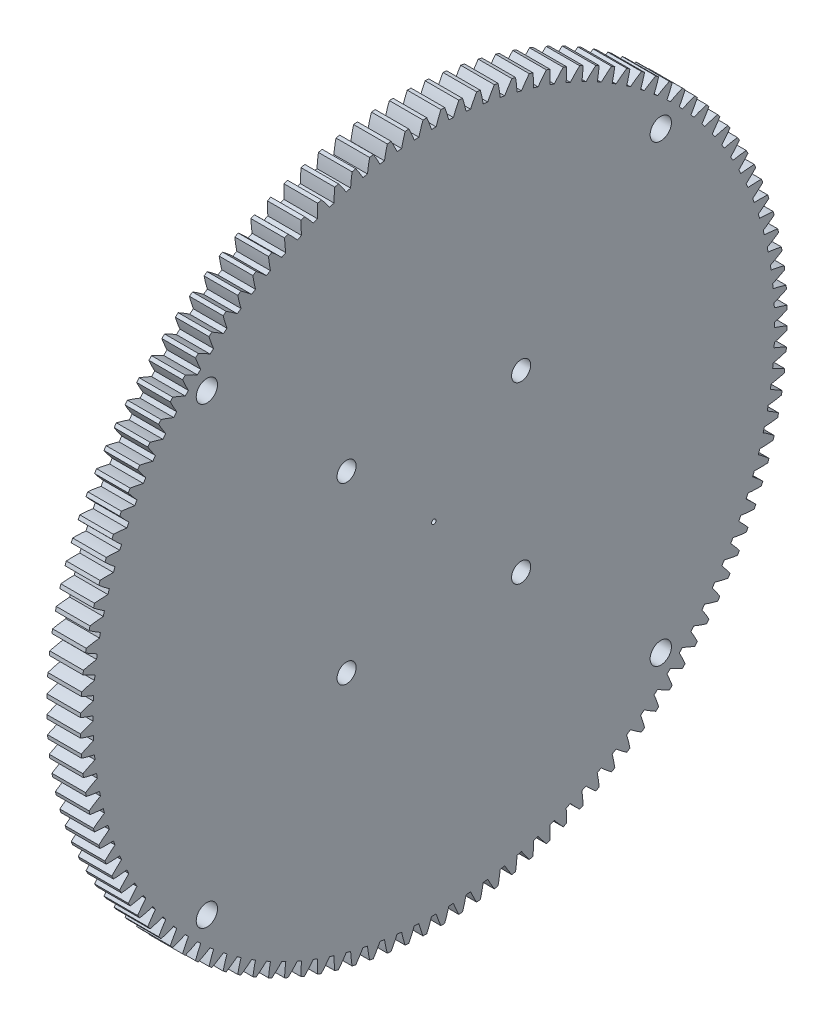
SolidWorks part; units mm, degrees
ref_plane "Plane1" through (0, 0, 0) normal (0, 0, 1) x (1, 0, 0)
ref_plane "Plane2" through (0, 0, 0) normal (0, 1, 0) x (1, 0, 0)
ref_plane "Plane3" through (0, 0, 0) normal (1, 0, 0) x (0, 0, -1)
sketch "HoldingSke" plane through (0, 0, 0) normal (0, 1, 0) x (1, 0, 0)
  line L0 (0, 0) -> (-0.5592, -0.829)
  line L1 (-15, 0) -> (100, 0) construction
  line L2 (0, 0) -> (-2.1039, 2.3779)
  line L3 (0, 0) -> (-11.863, 4.5341)
  line L4 (0, 0) -> (-4.8292, 7.1596)
  line L5 (0, 0) -> (-46.8476, -17.4728)
  line L6 (0, 0) -> (-4.9738, -3.3558)
  line L7 (-2.1039, 2.3779) -> (8.6586, 51.2059)
  line L8 (-76.2, 54.61) -> (-76.1, 54.61)
  line L9 (-71.009, 38.7566) -> (-53.1078, 45.2721)
  line L10 (-76.2, 71.12) -> (104.1128, 71.12)
  line L11 (0, 0) -> (-6, 0)
  line L12 (-76.2, 101.6) -> (-76.162, 101.6)
  line L13 (24.9733, 27.94) -> (52.9518, 28.4284)
  line L14 (24.9733, 27.94) -> (24.9743, 27.94)
  line L15 (24.9733, 27.94) -> (100.4006, 29.5858)
  line L16 (-63.627, -1) -> (-12.827, -1)
  circle A0 centre (0, 0) radius 0.4
  circle A1 centre (0, 0) radius 37.5
  circle A2 centre (0, 0) radius 37.5
  circle A3 centre (0, 0) radius 0.4
  dimension "Num_teeth" = 124
  dimension "Pitch_radius" = 180.3128
  dimension "Width" = 6
  dimension "Thickness" = 6
sketch "BasProSke" plane through (0, 0, 0) normal (0, 1, 0) x (1, 0, 0)
  line L0 (-10, 0) -> (60, 0) construction
  line L1 (0, 0) -> (0, 63)
  line L2 (0, 0) -> (6, 0)
  line L3 (6, 0) -> (6, 63)
  line L4 (6, 63) -> (0, 63)
  dimension "Thickness" = 6
  dimension "Diameter" = 126
revolve "Base-Revolve" add sketch "BasProSke" angle 360 about L0
sketch "TooCutSke" plane through (0, 0, 0) normal (1, 0, 0) x (0, 0, -1)
  line L1 (0, 0) -> (0, 107) construction
  line L2 (0, 0) -> (-0.8519, 61.9941) construction
  line L3 (0, 0) -> (-3.141, 123.9519) construction
  line L4 (-0.8519, 61.9941) -> (-1.5705, 61.9759) construction
  arc A0 (0.4101, 60.7476) -> (-0.4101, 60.7476) centre (0, 0) ccw
  arc A1 (1.2699, 63.0126) -> (-1.2699, 63.0126) centre (0, 0) ccw
  circle A2 centre (0, 0) radius 62 construction
  circle A3 centre (0, 0) radius 58.2609 construction
  arc A4 (-0.4101, 60.7476) -> (-1.2699, 63.0126) centre (-23.9979, 53.089) ccw
  arc A5 (1.2699, 63.0126) -> (0.4101, 60.7476) centre (23.9979, 53.089) ccw
extrude "ToothCut" cut sketch "TooCutSke" along normal through all
fillet "Breaks" [suppressed] radius 0.02 tangent propagation no
fillet "RootFillets" [suppressed] radius 0.251
pattern_circular "TeethCuts" count 124 every 2.903 about axis through (-10, 0, 0) along (1, 0, 0) of "ToothCut", "RootFillets", "Breaks"
sketch "HubNeaOneSke" plane through (0, 0, 0) normal (-1, 0, 0) x (0, 0, 1)
  circle A0 centre (0, 0) radius 37.5
  dimension "Diameter" = 75
extrude "HubNearOne" [suppressed] add sketch "HubNeaOneSke" along normal blind 44.0001
sketch "HubNeaBotSke" plane through (0, 0, 0) normal (-1, 0, 0) x (0, 0, 1)
  circle A0 centre (0, 0) radius 37.5
  dimension "Diameter" = 75
extrude "HubNearBoth" [suppressed] add sketch "HubNeaBotSke" along normal blind 22
ref_plane "FarPln" through (6, 0, 0) normal (1, 0, 0) x (0, 0, -1)
sketch "HubFarSke" plane through (6, 0, 0) normal (1, 0, 0) x (0, 0, -1)
  circle A0 centre (0, 0) radius 37.5
  dimension "Diameter" = 75
extrude "HubFar" [suppressed] add sketch "HubFarSke" along normal blind 22
sketch "BorSke" plane through (0, 0, 0) normal (1, 0, 0) x (0, 0, -1)
  circle A0 centre (0, 0) radius 0.4
  dimension "Diameter" = 0.8
extrude "Bore" cut sketch "BorSke" along normal mid plane 100.0001
sketch "KeySke" plane through (0, 0, 0) normal (1, 0, 0) x (0, 0, -1)
  line L0 (-0.05, 0) -> (-0.05, 0.5)
  line L1 (-0.05, 0.5) -> (0.05, 0.5)
  line L2 (0.05, 0.5) -> (0.05, 0)
  line L3 (0, 0) -> (0, 34) construction
  line L4 (-0.05, 0) -> (0.05, 0)
  dimension "Width" = 0.1
extrude "Keyway" [suppressed] cut sketch "KeySke" along normal mid plane 100.0001
pattern_circular "Keyway2" [suppressed] count 2 every 90 about axis through (-10, 0, 0) along (1, 0, 0) reverse direction yes
sketch "Sketch2" plane through (0, 0, 0) normal (-1, 0, 0) x (0, 0, 1)
  line L0 (0, 0) -> (-40.45, 40.45)
sketch "Sketch3" plane through (0, 0, 0) normal (-1, 0, 0) x (0, 0, 1)
  circle A0 centre (-40.45, 40.45) radius 1.9
extrude "Cut-Extrude2" cut sketch "Sketch3" against normal up to next contours A0
pattern_circular "CirPattern1" count 4 every 90 about axis through (50.0001, 0, 0) along (-1, 0, 0) of "Cut-Extrude2" reverse direction yes
sketch "Sketch4" plane through (0, 0, 0) normal (-1, 0, 0) x (0, 0, 1)
  line L0 (0, 0) -> (-15.5563, 15.5563)
  line L1 (0, 0) -> (-40.45, 40.45) construction
sketch "Sketch5" plane through (0, 0, 0) normal (-1, 0, 0) x (0, 0, 1)
  circle A0 centre (-15.5563, 15.5563) radius 1.7
extrude "Cut-Extrude3" cut sketch "Sketch5" against normal up to next
pattern_circular "CirPattern2" count 4 every 90 about axis through (50.0001, 0, 0) along (-1, 0, 0) of "Cut-Extrude3" reverse direction yes
equation "' \"Module@HoldingSke\" = 6.35"
equation "' \"Num_teeth@HoldingSke\" = 12"
equation "' \"Ap@HoldingSke\" =  20"
equation "' \"Ap@HoldingSke\" = 20"
equation "' \"Width@HoldingSke\" = 0.5 * 25.4"
equation "' \"Hub_dia@HoldingSke\"= 1 * 25.4"
equation "' \"Hub_dia@HoldingSke\" = 1 * 25.4"
equation "' \"Overall_len@HoldingSke\" = 1.0 * 25.4"
equation "' \"Bore@HoldingSke\" = 0.75 * 25.4"
equation "' \"T_dim@HoldingSke\" = 0.1 * 25.4"
equation "' \"Width@KeySke\" = 0.25 * 25.4"
equation "' \"Show_teeth@HoldingSke\" = 13"
equation "' \"Backlash@HoldingSke\" = 0.009 * 25.4"
equation "' \"Addendum_fac@HoldingSke\" = 1.0"
equation "' \"Dedendum_fac@HoldingSke\" = 1.25"
equation "' \"Dedendum_add@HoldingSke\" = 0.00005 * 25.4"
equation "' \"Clearance_fac@HoldingSke\" = 0.25"
equation "\"Pitch@HoldingSke\" = 1 / \"Module@HoldingSke\""
equation "\"Overcut_dia@TooCutSke\" = (\"Num_teeth@HoldingSke\" + 2 * \"Addendum_fac@HoldingSke\") / \"Pitch@HoldingSke\" + 0.002 * 25.4"
equation "\"Pitch_dia@TooCutSke\" = \"Num_teeth@HoldingSke\" / \"Pitch@HoldingSke\""
equation "\"Base_dia@TooCutSke\" = \"Num_teeth@HoldingSke\" / \"Pitch@HoldingSke\" * cos((\"Ap@HoldingSke\"  * 3.14159265 / 180))"
equation "\"Root_dia@TooCutSke\" = (\"Num_teeth@HoldingSke\" + 2) / \"Pitch@HoldingSke\" - 2 * (\"Addendum_fac@HoldingSke\" + \"Dedendum_fac@HoldingSke\") / \"Pitch@HoldingSke\" - \"Dedendum_add@HoldingSke\" * 2"
equation "\"Half_ang@TooCutSke\" = 180 / \"Num_teeth@HoldingSke\""
equation "\"Half_CT@TooCutSke\" = \"Num_teeth@HoldingSke\" / \"Pitch@HoldingSke\" * sin((3.14159265 / 2 / \"Num_teeth@HoldingSke\")) / 2 - 7 * \"Backlash@HoldingSke\" / 4"
equation "\"Flank_rad@TooCutSke\" = \"Num_teeth@HoldingSke\" / \"Pitch@HoldingSke\" / 5"
equation "\"Radius@RootFillets\" = \"Clearance_fac@HoldingSke\" / \"Pitch@HoldingSke\" + \"Dedendum_add@HoldingSke\""
equation "\"Break_rad@Breaks\" = 0.02 / \"Pitch@HoldingSke\""
equation "\"Thickness@HoldingSke\" = \"Width@HoldingSke\""
equation "\"OAL@HoldingSke\" = \"Thickness@HoldingSke\""
equation "\"MHD@HoldingSke\" = (\"Num_teeth@HoldingSke\" + 2) / \"Pitch@HoldingSke\" - 2 * (\"Addendum_fac@HoldingSke\" + \"Dedendum_fac@HoldingSke\")  / \"Pitch@HoldingSke\" - \"Dedendum_add@HoldingSke\" * 2"
equation "\"MBD@HoldingSke\" = (\"Num_teeth@HoldingSke\" + 2) / \"Pitch@HoldingSke\" - 2 * (\"Addendum_fac@HoldingSke\" + \"Dedendum_fac@HoldingSke\")  / \"Pitch@HoldingSke\" - \"Dedendum_add@HoldingSke\" * 2 - 0.002 * 25.4"
equation "\"MHD@HoldingSke\" = ((sgn( \"MHD@HoldingSke\" - \"Hub_dia@HoldingSke\" )-1)*( \"MHD@HoldingSke\" - \"Hub_dia@HoldingSke\" ))/-2+ \"Hub_dia@HoldingSke\""
equation "\"MBD@HoldingSke\" = ((sgn( \"MBD@HoldingSke\" - \"Bore@HoldingSke\" )-1)*( \"MBD@HoldingSke\" - \"Bore@HoldingSke\" ))/-2+ \"Bore@HoldingSke\""
equation "\"OAL@HoldingSke\" = ((sgn( \"OAL@HoldingSke\" - \"Overall_len@HoldingSke\" )+1)*( \"OAL@HoldingSke\" - \"Overall_len@HoldingSke\" ))/2 + \"Overall_len@HoldingSke\" + 0.000002 * 25.4"
equation "\"Num_teeth@TeethCuts\" = int( \"Show_teeth@HoldingSke\" ) + 1"
equation "\"Num_teeth@TeethCuts\" = ((sgn( \"Num_teeth@TeethCuts\" - \"Num_teeth@HoldingSke\" )-1)*( \"Num_teeth@TeethCuts\" - \"Num_teeth@HoldingSke\" ))/-2+ \"Num_teeth@HoldingSke\""
equation "\"Num_teeth@TeethCuts\" = ((sgn( \"Num_teeth@TeethCuts\" - 2.0)+1)*( \"Num_teeth@TeethCuts\" - 2.0))/2 +2.0"
equation "\"Angle@TeethCuts\" = 360.0 / \"Num_teeth@HoldingSke\""
equation "\"Diameter@BasProSke\" = (\"Num_teeth@HoldingSke\" + 2 * \"Addendum_fac@HoldingSke\") / \"Pitch@HoldingSke\""
equation "\"Thickness@BasProSke\"  = \"Thickness@HoldingSke\""
equation "' \"Fillet_rad@BasProSke\" =  \"Thickness@HoldingSke\" * 0.05"
equation "' \"Fillet_rad@BasProSke\" = \"Thickness@HoldingSke\" * 0.05"
equation "\"MHD@HoldingSke\" = ((sgn( \"MHD@HoldingSke\" - \"Root_dia@TooCutSke\" )-1)*( \"MHD@HoldingSke\" - \"Root_dia@TooCutSke\" ))/-2+ \"Root_dia@TooCutSke\""
equation "\"Diameter@HubNeaOneSke\" = \"MHD@HoldingSke\""
equation "\"Length@HubNearOne\" = \"OAL@HoldingSke\" - \"Thickness@BasProSke\""
equation "\"Diameter@HubNeaBotSke\" = \"MHD@HoldingSke\""
equation "\"Length@HubNearBoth\" = ( \"OAL@HoldingSke\" - \"Thickness@BasProSke\" ) / 2.0"
equation "\"Thickness@FarPln\" = \"Thickness@BasProSke\""
equation "\"Diameter@HubFarSke\" = \"MHD@HoldingSke\""
equation "\"Length@HubFar\" = ( \"OAL@HoldingSke\" - \"Thickness@BasProSke\" ) / 2.0"
equation "\"Diameter@BorSke\" = \"MBD@HoldingSke\""
equation "\"D1@Bore\" = \"OAL@HoldingSke\" * 2.0"
equation "\"D1@Keyway\" = \"OAL@HoldingSke\" * 2.0"
equation "\"Offset@KeySke\" = \"T_dim@HoldingSke\" + \"MBD@HoldingSke\" / 2.0"
